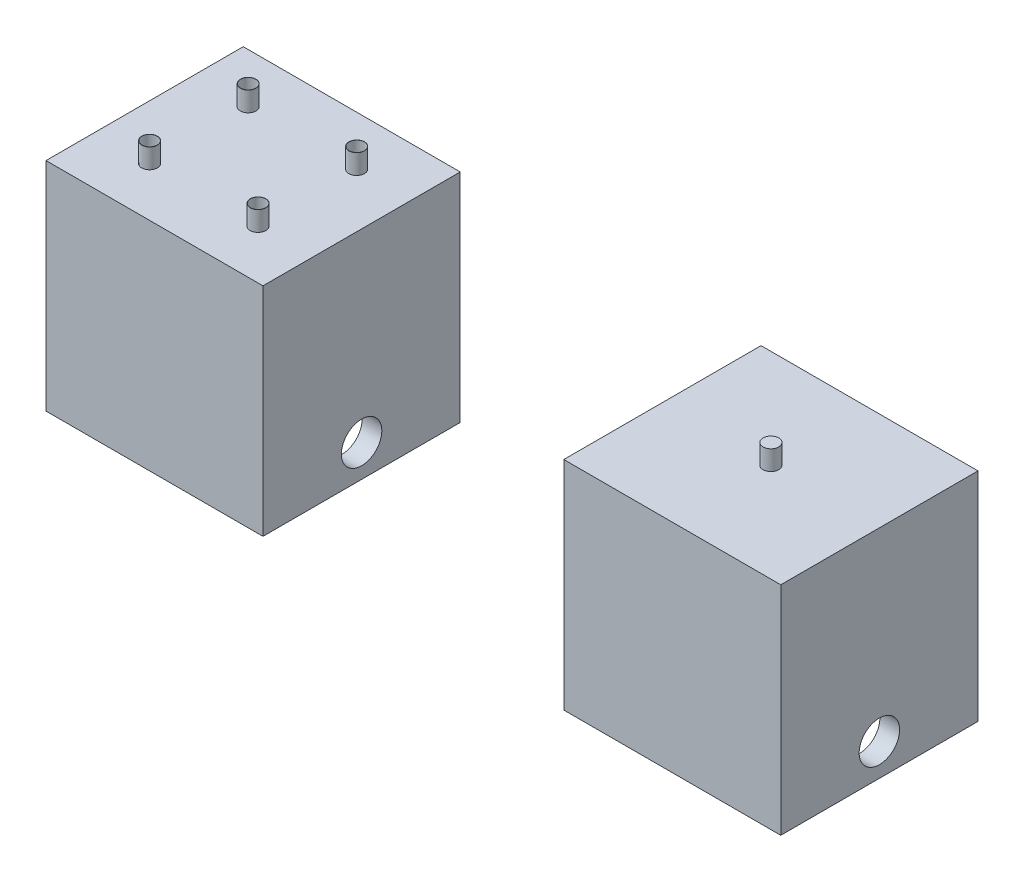
SolidWorks part; units mm, degrees
note: The reader was unsure of these and kept them because the rebuilt part matched: shared geometry of "Sketch11<2>", "Sketch11<3>".
ref_plane "Front Plane" through (0, 0, 0) normal (0, 0, 1) x (1, 0, 0)
ref_plane "Top Plane" through (0, 0, 0) normal (0, 1, 0) x (1, 0, 0)
ref_plane "Right Plane" through (0, 0, 0) normal (1, 0, 0) x (0, 0, -1)
sketch "Sketch1" plane through (0, 0, 0) normal (0, 0, 1) x (1, 0, 0)
  line L0 (0, 0) -> (-24.0497, 0) construction
  line L1 (0, 0) -> (0, 12.9433) construction
  line L2 (-15.25, 7.6464) -> (-15.25, -10.9356) construction
  line L3 (-37.25, 6.493) -> (-37.25, -9.7822) construction
  line L4 (-38.8193, -22) -> (7.2777, -22) construction
  line L5 (-38.8193, -5) -> (7.2777, -5) construction
  line L6 (37.25, 0) -> (-37.25, 0)
  line L7 (-37.25, 0) -> (-37.25, -22)
  line L8 (-37.25, -22) -> (-15.25, -22)
  line L9 (-15.25, -22) -> (-15.25, -5)
  line L10 (-15.25, -5) -> (15.25, -5)
  line L11 (15.25, -22) -> (15.25, -5)
  line L12 (37.25, -22) -> (15.25, -22)
  line L13 (37.25, 0) -> (37.25, -22)
  point P21 (0, -5)
  point P24 (0, 0)
  dimension "D1" = 15.25
  dimension "D2" = 22
  dimension "D3" = 5
  dimension "D4" = 22
extrude "Boss-Extrude1" add sketch "Sketch1" along normal blind 20
sketch "Sketch3" plane through (0, 0, 0) normal (0, 1, 0) x (1, 0, 0)
  line L0 (0, 0) -> (0, -29.5064) construction
  line L1 (0, 0) -> (-49.8183, 0) construction
  line L3 (-15.25, -0.4517) -> (-15.25, -27.0115) construction
  line L5 (-37.25, 0) -> (-37.25, -27.7392) construction
  line L6 (-30.4832, -20) -> (-53.7685, -20) construction
  line L8 (-42.2298, -18) -> (-12.1875, -18) construction
  line L9 (-35.25, -20.8783) -> (-35.25, 1.9912) construction
  line L10 (-17.25, -20.8783) -> (-17.25, 1.9912) construction
  line L11 (-38.9532, -2) -> (-13.3501, -2) construction
  line L12 (-35.25, -18) -> (-17.25, -18)
  line L13 (-17.25, -18) -> (-17.25, -2)
  line L14 (-17.25, -2) -> (-35.25, -2)
  line L15 (-35.25, -2) -> (-35.25, -18)
  line L16 (35.25, -2) -> (35.25, -18)
  line L17 (17.25, -2) -> (35.25, -2)
  line L18 (17.25, -18) -> (17.25, -2)
  line L19 (35.25, -18) -> (17.25, -18)
  dimension "D1" = 15.25
  dimension "D2" = 2
  dimension "D3" = 20
  dimension "D4" = 2
  dimension "D5" = 22
  dimension "D6" = 2
  dimension "D7" = 2
extrude "Cut-Extrude2" cut sketch "Sketch3" along normal blind 15 from surface at -22 starting at face at (-26.25, -22, 10)
sketch "Sketch4" plane through (0, 0, 0) normal (0, 1, 0) x (1, 0, 0)
  line L0 (0, 0) -> (0, -24.068) construction
  line L2 (0, 0) -> (-45.1812, 0) construction
  line L3 (-27.5419, -20) -> (-60.0716, -20) construction
  line L5 (-37.25, -14.8284) -> (-37.25, 12.4324) construction
  line L7 (-15.25, -20) -> (-15.25, 1.6685) construction
  line L8 (-26.25, 1.2831) -> (-26.25, -23.7598) construction
  line L9 (-38.9425, -10) -> (-8.9169, -10) construction
  line L10 (-31.75, 0.763) -> (-31.75, -22.3468) construction
  line L11 (-39.4111, -5) -> (-18.6017, -5) construction
  line L12 (15.25, -0.5674) -> (15.25, -23.9132) construction
  line L14 (37.25, -0.5674) -> (37.25, -23.5193) construction
  line L16 (26.25, 0.9295) -> (26.25, -23.9606) construction
  circle A0 centre (-31.75, -5) radius 0.7937
  circle A1 centre (-20.75, -5) radius 0.7937
  circle A2 centre (-20.75, -15) radius 0.7937
  circle A3 centre (-31.75, -15) radius 0.7937
  circle A8 centre (26.25, -10) radius 0.7937
  dimension "D8" = 1.5875
  dimension "D12" = 1.5875
  dimension "D1" = 37.25
  dimension "D2" = 20
  dimension "D3" = 15.25
  dimension "D4" = 11
  dimension "D5" = 10
  dimension "D6" = 5
  dimension "D7" = 5.5
  dimension "D9" = 15.25
  dimension "D10" = 22
  dimension "D11" = 11
extrude "Cut-Extrude3" cut sketch "Sketch4" against normal through all from surface at 0 starting at face at (0, 0, 10)
sketch "Sketch5" plane through (0, 0, 0) normal (0, 1, 0) x (1, 0, 0)
  line L0 (0, 0) -> (0, -23.0593) construction
  line L1 (0, 0) -> (-42.7755, 0) construction
  line L2 (0, -10) -> (-44.3779, -10) construction
  line L3 (-26.25, 0.9213) -> (-26.25, -21.8437) construction
  line L4 (-15.25, -1.9519) -> (-15.25, 8.9333) construction
  line L5 (26.25, 0.9213) -> (26.25, -21.8437) construction
  line L6 (-37.25, -5.875) -> (-37.25, 9.7621) construction
  line L7 (0, -10) -> (44.3779, -10) construction
  line L8 (-29.9563, -20) -> (-46.4223, -20) construction
  circle A0 centre (-31.75, -5) radius 0.7937
  circle A1 centre (-31.75, -5) radius 0.7737
  circle A2 centre (-20.75, -5) radius 0.7737
  circle A3 centre (-20.75, -5) radius 0.7937
  circle A4 centre (-20.75, -15) radius 0.7937
  circle A5 centre (-20.75, -15) radius 0.7737
  circle A6 centre (-31.75, -15) radius 0.7737
  circle A7 centre (-31.75, -15) radius 0.7937
  circle A16 centre (26.25, -10) radius 0.7937
  dimension "D1" = 1.5875
  dimension "D2" = 0.02
  dimension "D8" = 1.5875
  dimension "D3" = 15.25
  dimension "D4" = 22
  dimension "D5" = 11
  dimension "D6" = 20
  dimension "D7" = 10
extrude "Boss-Extrude3" add sketch "Sketch5" along normal blind 2
sketch "Sketch6" plane through (0, 0, 0) normal (0, 1, 0) x (1, 0, 0)
  line L0 (0, 0) -> (0, -26.198) construction
  line L1 (-2.1363, 0) -> (44.2613, 0) construction
  line L3 (-15.25, -5.376) -> (-15.25, -30.5554) construction
  line L5 (15.25, -10.4004) -> (15.25, -27.3009) construction
  line L7 (-11.1442, -10) -> (8.8394, -10) construction
  circle A0 centre (0, -10) radius 2.05
  dimension "D4" = 4.1
  dimension "D1" = 15.25
  dimension "D2" = 15.25
  dimension "D3" = 10
sketch "Sketch11" plane through (0, 0, 0) normal (1, 0, 0) x (0, 0, -1)
  line L0 (-14.3729, -22) -> (8.4563, -22) construction
  line L2 (-10.7583, -18.75) -> (9.4401, -18.75) construction
  line L3 (0, 0) -> (-29.0876, 0) construction
  line L4 (0, 0) -> (0, -31.8739) construction
  line L5 (-20, 0) -> (-20, -30.048) construction
  line L6 (-10, 0) -> (-10, -31.8739) construction
  circle A0 centre (-10, -18.75) radius 2.05
  dimension "D5" = 4.1
  dimension "D1" = 22
  dimension "D2" = 3.25
  dimension "D3" = 20
  dimension "D4" = 10
extrude "Cut-Extrude6" cut sketch "Sketch11" against normal up to next from surface
extrude "Cut-Extrude7" cut sketch "Sketch11<2>" along normal up to next from surface
sketch "Sketch11<2>" plane through (0, 0, 0) normal (1, 0, 0) x (0, 0, -1) same geometry as "Sketch11"
extrude "Cut-Extrude8" cut sketch "Sketch11<3>" along normal up to next and the other way up to next from surface
sketch "Sketch11<3>" plane through (0, 0, 0) normal (1, 0, 0) x (0, 0, -1) same geometry as "Sketch11"
extrude "Cut-Extrude9" cut sketch "Sketch6" against normal through all
sketch "Sketch12" plane through (0, 0, 0) normal (0, 1, 0) x (1, 0, 0)
  line L0 (-15.25, 0) -> (15.25, 0)
  line L1 (15.25, 0) -> (15.25, -20)
  line L2 (15.25, -20) -> (-15.25, -20)
  line L3 (-15.25, -20) -> (-15.25, 0)
extrude "Cut-Extrude10" cut sketch "Sketch12" against normal through all
